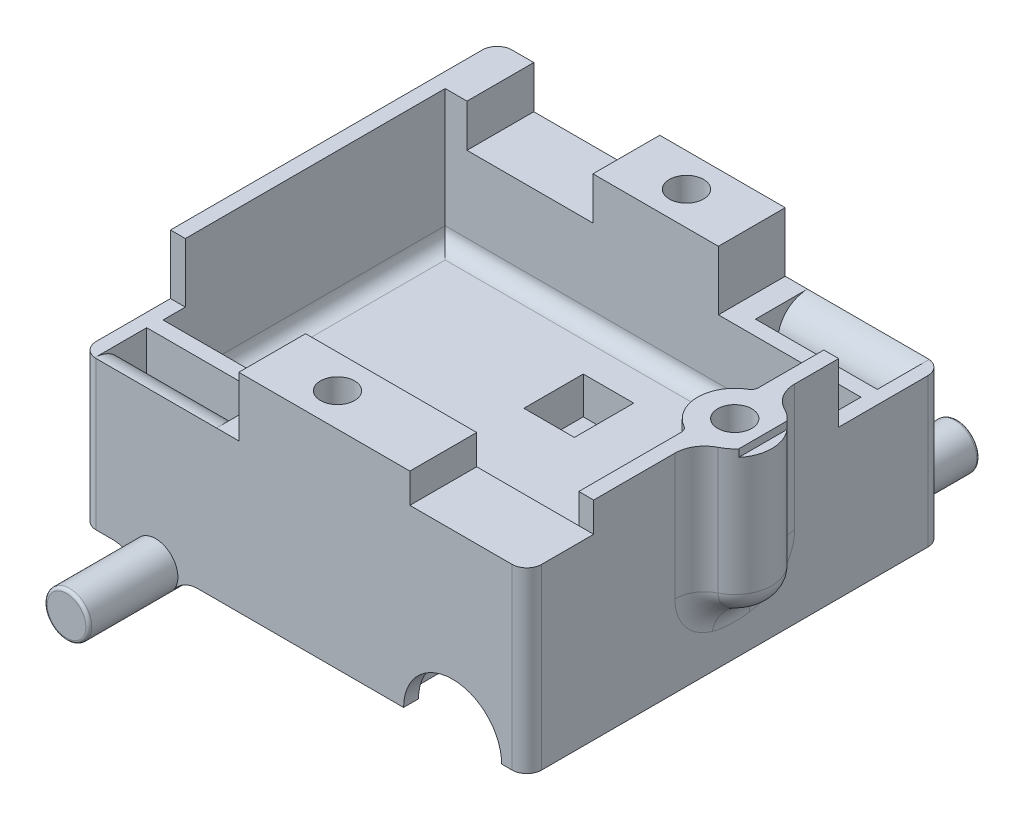
SolidWorks part; units mm, degrees
ref_plane "Front Plane" through (0, 0, 0) normal (0, 0, 1) x (1, 0, 0)
ref_plane "Top Plane" through (0, 0, 0) normal (0, 1, 0) x (1, 0, 0)
ref_plane "Right Plane" through (0, 0, 0) normal (1, 0, 0) x (0, 0, -1)
sketch "Sketch4" plane through (0, 0, 0) normal (0, 1, 0) x (1, 0, 0)
  line L1 (-14.8464, 7.0648) -> (15.1536, 7.0648)
  line L2 (-14.8464, 7.0648) -> (-14.8464, -20.9352)
  line L3 (-14.8464, -20.9352) -> (15.1536, -20.9352)
  line L4 (15.1536, 7.0648) -> (15.1536, -20.9352)
  dimension "D1" = 30
  dimension "D2" = 28
extrude "Boss-Extrude2" add sketch "Sketch4" along normal blind 14
sketch "Sketch20" plane through (0, 14, 0) normal (0, 1, 0) x (1, 0, 0)
  line L0 (-14.8464, -20.9352) -> (15.1536, -20.9352) construction
  line L1 (14.1536, -16.4352) -> (-13.8464, -16.4352)
  line L2 (14.1536, -16.4352) -> (14.1536, 2.5648)
  line L3 (14.1536, 2.5648) -> (-13.8464, 2.5648)
  line L4 (-13.8464, -16.4352) -> (-13.8464, 2.5648)
  line L5 (15.1536, -20.9352) -> (15.1536, 7.0648) construction
  dimension "D1" = 19
  dimension "D2" = 4.5
  dimension "D3" = 28
  dimension "D4" = 1
extrude "Cut-Extrude16" cut sketch "Sketch20" against normal blind 9
fillet "Fillet10" radius 1 4 edges at (0.1536, 5, 16.4352) (-13.8464, 5, 6.9352) (0.1536, 5, -2.5648) (14.1536, 5, 6.9352)
sketch "Sketch26" plane through (0, 0, 20.9352) normal (0, 0, 1) x (1, 0, 0)
  circle A0 centre (10.1536, 0) radius 4.1
  dimension "D1" = 8.2
extrude "Cut-Extrude17" cut sketch "Sketch26" against normal blind 26
sketch "Sketch27" plane through (0, 0, -7.0648) normal (0, 0, -1) x (-1, 0, 0)
  circle A0 centre (9.8464, 0) radius 4.1
  dimension "D1" = 8.2
extrude "Cut-Extrude18" cut sketch "Sketch27" against normal blind 26
sketch "Sketch28" plane through (0, 0, 0) normal (0, -1, 0) x (1, 0, 0)
  line L0 (-5.7464, 18.9352) -> (-5.7464, -7.0648) construction
  line L1 (-13.9464, -7.0648) -> (-5.7464, -7.0648)
  line L2 (-13.9464, -7.0648) -> (-13.9464, -6.0648)
  line L3 (-13.9464, -6.0648) -> (-5.7464, -6.0648)
  line L4 (-5.7464, -7.0648) -> (-5.7464, -6.0648)
  line L5 (14.2536, 20.9352) -> (14.2536, -5.0648) construction
  line L6 (6.0536, 20.9352) -> (14.2536, 20.9352)
  line L7 (6.0536, 20.9352) -> (6.0536, 19.9352)
  line L8 (6.0536, 19.9352) -> (14.2536, 19.9352)
  line L9 (14.2536, 20.9352) -> (14.2536, 19.9352)
  dimension "D1" = 1
  dimension "D2" = 1
extrude "Boss-Extrude6" add sketch "Sketch28" against normal blind 9
sketch "Sketch29" plane through (0, 0, -7.0648) normal (0, 0, -1) x (-1, 0, 0)
  circle A0 centre (9.8464, 0) radius 3.3
  dimension "D1" = 6.6
extrude "Cut-Extrude19" cut sketch "Sketch29" against normal blind 1
sketch "Sketch30" plane through (0, 0, 20.9352) normal (0, 0, 1) x (1, 0, 0)
  circle A0 centre (10.1536, 0) radius 3.3
  dimension "D1" = 6.6
extrude "Cut-Extrude20" cut sketch "Sketch30" against normal blind 1
sketch "Sketch31" plane through (0, 0, 18.9352) normal (0, 0, -1) x (-1, 0, 0)
  line L0 (5.7464, 0) -> (13.9464, 0) construction
  circle A0 centre (9.8464, 0) radius 1.5
  dimension "D1" = 3
extrude "Boss-Extrude7" add sketch "Sketch31" against normal blind 8
sketch "Sketch32" plane through (0, 0, -5.0648) normal (0, 0, 1) x (1, 0, 0)
  line L0 (6.0536, 0) -> (14.2536, 0) construction
  circle A0 centre (10.1536, 0) radius 1.5
  dimension "D1" = 3
extrude "Boss-Extrude8" add sketch "Sketch32" against normal blind 8
fillet "Fillet12" radius 2 2 edges at (8.6536, 0, -6.0648) (-8.3464, 0, 19.9352)
sketch "Sketch33" plane through (0, 0, 0) normal (0, -1, 0) x (1, 0, 0)
  line L0 (14.2536, 19.9352) -> (14.2536, -5.0648) construction
  line L1 (6.0536, -5.0648) -> (14.2536, -5.0648)
  line L2 (6.0536, -5.0648) -> (6.0536, -3.5648)
  line L3 (6.0536, -3.5648) -> (14.2536, -3.5648)
  line L4 (14.2536, -5.0648) -> (14.2536, -3.5648)
  line L5 (-13.9464, -6.0648) -> (-13.9464, 18.9352) construction
  line L6 (-5.7464, 18.9352) -> (-13.9464, 18.9352)
  line L7 (-5.7464, 18.9352) -> (-5.7464, 17.4352)
  line L8 (-5.7464, 17.4352) -> (-13.9464, 17.4352)
  line L9 (-13.9464, 18.9352) -> (-13.9464, 17.4352)
  dimension "D1" = 1.5
  dimension "D2" = 1.5
extrude "Cut-Extrude21" cut sketch "Sketch33" against normal through all
fillet "Fillet13" radius 0.2 2 edges at (11.6536, 0, -13.0648) (-11.3464, 0, 26.9352)
fillet "Fillet15" radius 1 4 edges at (15.1536, 7, 20.9352) (15.1536, 7, -7.0648) (-14.8464, 7, -7.0648) (-14.8464, 7, 20.9352)
sketch "Sketch34" plane through (0, 14, 0) normal (0, 1, 0) x (1, 0, 0)
  line L0 (15.1536, -19.9352) -> (15.1536, 6.0648) construction
  circle A0 centre (15.1536, -6.9352) radius 2.5
  dimension "D1" = 5
extrude "Boss-Extrude9" add sketch "Sketch34" against normal blind 10
fillet "Fillet16" radius 1.5 1 edges at (17.6536, 4, 6.9352)
fillet "Fillet17" radius 2 5 edges at (15.1536, 9.75, 9.4352) (15.1536, 9.75, 4.4352) (15.1536, 4.4393, 8.9958) (15.1536, 4.4393, 4.8745) (15.1536, 4, 6.9352)
fillet "Fillet18" radius 0.5 5 edges at (13.9723, 5.4258, 9.1384) (13.8531, 5.2853, 4.8001) (14.1536, 10, 9.2264) (14.1536, 10, 4.6439) (12.6536, 5, 6.9352)
sketch "Sketch35" plane through (0, 14, 0) normal (0, 1, 0) x (1, 0, 0)
  circle A0 centre (15.1536, -6.9352) radius 1.15
  dimension "D1" = 2.3
extrude "Cut-Extrude22" cut sketch "Sketch35" against normal blind 8
sketch "Sketch36" plane through (0, 14, 0) normal (0, 1, 0) x (1, 0, 0)
  line L0 (14.1536, 2.5648) -> (-13.8464, 2.5648) construction
  line L1 (-14.8464, 6.0648) -> (-14.8464, -19.9352) construction
  line L2 (-13.8464, -20.9352) -> (14.1536, -20.9352) construction
  circle A0 centre (0.1536, -18.6852) radius 1.15
  circle A1 centre (0.1536, 4.8148) radius 1.15
  dimension "D1" = 2.3
  dimension "D2" = 2.3
  dimension "D3" = 2.25
  dimension "D4" = 15
  dimension "D5" = 2.25
  dimension "D6" = 15
extrude "Cut-Extrude23" cut sketch "Sketch36" against normal through all
sketch "Sketch37" plane through (0, 0, -5.0648) normal (0, 0, 1) x (1, 0, 0)
  line L0 (14.2536, 14) -> (14.2536, 0) construction
  line L1 (6.0536, 14) -> (14.2536, 14)
  line L2 (6.0536, 14) -> (6.0536, 10)
  line L3 (6.0536, 10) -> (14.2536, 10)
  line L4 (14.2536, 14) -> (14.2536, 10)
  dimension "D1" = 4
extrude "Cut-Extrude24" cut sketch "Sketch37" against normal blind 2
fillet "Fillet19" radius 2 1 edges at (10.1536, 10, -5.0648)
sketch "Sketch38" plane through (0, 0, 18.9352) normal (0, 0, -1) x (-1, 0, 0)
  line L0 (13.9464, 14) -> (13.9464, 0) construction
  line L1 (5.7464, 14) -> (13.9464, 14)
  line L2 (5.7464, 14) -> (5.7464, 10)
  line L3 (5.7464, 10) -> (13.9464, 10)
  line L4 (13.9464, 14) -> (13.9464, 10)
  dimension "D1" = 4
extrude "Cut-Extrude25" cut sketch "Sketch38" against normal blind 2
fillet "Fillet20" radius 2 1 edges at (-9.8464, 10, 18.9352)
sketch "Sketch39" plane through (0, 0, 0) normal (0, -1, 0) x (1, 0, 0)
  line L0 (15.1536, 19.9352) -> (15.1536, -6.0648) construction
  line L1 (7.2813, -7.0648) -> (-6.5464, -7.0648) construction
  line L2 (-6.9741, 20.9352) -> (6.8536, 20.9352) construction
  circle A0 centre (0.1536, 2.4352) radius 0.9
  circle A2 centre (0.1536, 11.4352) radius 0.9
  dimension "D1" = 15
  dimension "D2" = 15
  dimension "D3" = 9.5
  dimension "D4" = 9.5
  dimension "D5" = 1.8
  dimension "D6" = 1.8
extrude "Cut-Extrude26" cut sketch "Sketch39" against normal through all and the other way through all
sketch "Sketch40" plane through (0, 5, 0) normal (0, 1, 0) x (1, 0, 0)
  line L1 (-1.5464, -0.4352) -> (1.8536, -0.4352)
  line L2 (-1.5464, -0.4352) -> (-1.5464, -4.4352)
  line L3 (-1.5464, -4.4352) -> (1.8536, -4.4352)
  line L4 (1.8536, -0.4352) -> (1.8536, -4.4352)
  line L5 (-1.5464, -9.4352) -> (1.8536, -9.4352)
  line L6 (-1.5464, -9.4352) -> (-1.5464, -13.4352)
  line L7 (-1.5464, -13.4352) -> (1.8536, -13.4352)
  line L8 (1.8536, -9.4352) -> (1.8536, -13.4352)
  circle A0 centre (0.1536, -2.4352) radius 0.9 construction
  circle A1 centre (0.1536, -11.4352) radius 0.9 construction
  dimension "D1" = 3.4
  dimension "D2" = 3.4
  dimension "D3" = 4
  dimension "D4" = 4
  dimension "D5" = 2
  dimension "D6" = 1.7
  dimension "D7" = 1.7
  dimension "D8" = 2
extrude "Cut-Extrude27" cut sketch "Sketch40" against normal blind 2.5
sketch "Sketch41" plane through (0, 0, -7.0648) normal (0, 0, -1) x (-1, 0, 0)
  line L0 (-6.0536, 14) -> (13.8464, 14) construction
  line L1 (3.8964, 14) -> (12.3775, 14)
  line L2 (3.8964, 14) -> (3.8964, 11.1303)
  line L3 (3.8964, 11.1303) -> (12.3775, 11.1303)
  line L4 (12.3775, 14) -> (12.3775, 11.1303)
extrude "Cut-Extrude28" cut sketch "Sketch41" against normal blind 10
sketch "Sketch42" plane through (0, 0, -7.0648) normal (0, 0, -1) x (-1, 0, 0)
  line L1 (-6.0536, 10) -> (-16.2647, 10)
  line L2 (-6.0536, 10) -> (-6.0536, 14)
  line L3 (-6.0536, 14) -> (-16.2647, 14)
  line L4 (-16.2647, 10) -> (-16.2647, 14)
extrude "Cut-Extrude29" cut sketch "Sketch42" against normal blind 7
sketch "Sketch43" plane through (0, 14, 0) normal (0, 1, 0) x (1, 0, 0)
  line L0 (15.1536, -19.9352) -> (15.1536, -10.9663) construction
  line L1 (15.1536, -16.4352) -> (7.2753, -16.4352)
  line L2 (15.1536, -16.4352) -> (15.1536, -20.9352)
  line L3 (15.1536, -20.9352) -> (7.2753, -20.9352)
  line L4 (7.2753, -16.4352) -> (7.2753, -20.9352)
  line L5 (-5.7464, -20.9352) -> (14.1536, -20.9352) construction
extrude "Cut-Extrude30" cut sketch "Sketch43" against normal blind 2
sketch "Sketch44" plane through (0, 14, 0) normal (0, 1, 0) x (1, 0, 0)
  line L1 (17.052, -8.7906) -> (17.8177, -8.7906)
  line L2 (17.052, -8.7906) -> (17.052, -5.0159)
  line L3 (17.052, -5.0159) -> (17.8177, -5.0159)
  line L4 (17.8177, -8.7906) -> (17.8177, -5.0159)
extrude "Cut-Extrude31" cut sketch "Sketch44" against normal blind 0.5
sketch "Sketch45" plane through (0, 0, 20.9352) normal (0, 0, 1) x (1, 0, 0)
  line L1 (-5.7464, 10) -> (-15.5344, 10)
  line L2 (-5.7464, 10) -> (-5.7464, 14)
  line L3 (-5.7464, 14) -> (-15.5344, 14)
  line L4 (-15.5344, 10) -> (-15.5344, 14)
extrude "Cut-Extrude32" cut sketch "Sketch45" against normal up to surface (3.5 mm away) up to face at (-9.8464, 8.025, 17.4352)
sketch "Sketch46" plane through (0, 0, 20.9352) normal (0, 0, 1) x (1, 0, 0)
  line L0 (-5.7464, 14) -> (7.2753, 14) construction
  line L1 (-5.7464, 10) -> (-4.2464, 10)
  line L2 (-5.7464, 10) -> (-5.7464, 14)
  line L3 (-5.7464, 14) -> (-4.2464, 14)
  line L4 (-4.2464, 10) -> (-4.2464, 14)
  dimension "D1" = 1.5
extrude "Cut-Extrude33" cut sketch "Sketch46" against normal up to surface (3.5 mm away) up to face at (-11.5131, 8.6833, 17.4352)
sketch "Sketch47" plane through (0, 0, 17.4352) normal (0, 0, 1) x (1, 0, 0)
  line L1 (-14.8464, 10) -> (-4.2464, 10)
  line L2 (-14.8464, 10) -> (-14.8464, 14)
  line L3 (-14.8464, 14) -> (-4.2464, 14)
  line L4 (-4.2464, 10) -> (-4.2464, 14)
extrude "Cut-Extrude34" cut sketch "Sketch47" against normal blind 2.5
sketch "Sketch48" plane through (0, 0, -7.0648) normal (0, 0, -1) x (-1, 0, 0)
  line L0 (-6.0536, 14) -> (3.8964, 14) construction
  line L1 (-6.0536, 10) -> (-4.5536, 10)
  line L2 (-6.0536, 10) -> (-6.0536, 14)
  line L3 (-6.0536, 14) -> (-4.5536, 14)
  line L4 (-4.5536, 10) -> (-4.5536, 14)
  dimension "D1" = 1.5
extrude "Cut-Extrude35" cut sketch "Sketch48" against normal blind 4.5
